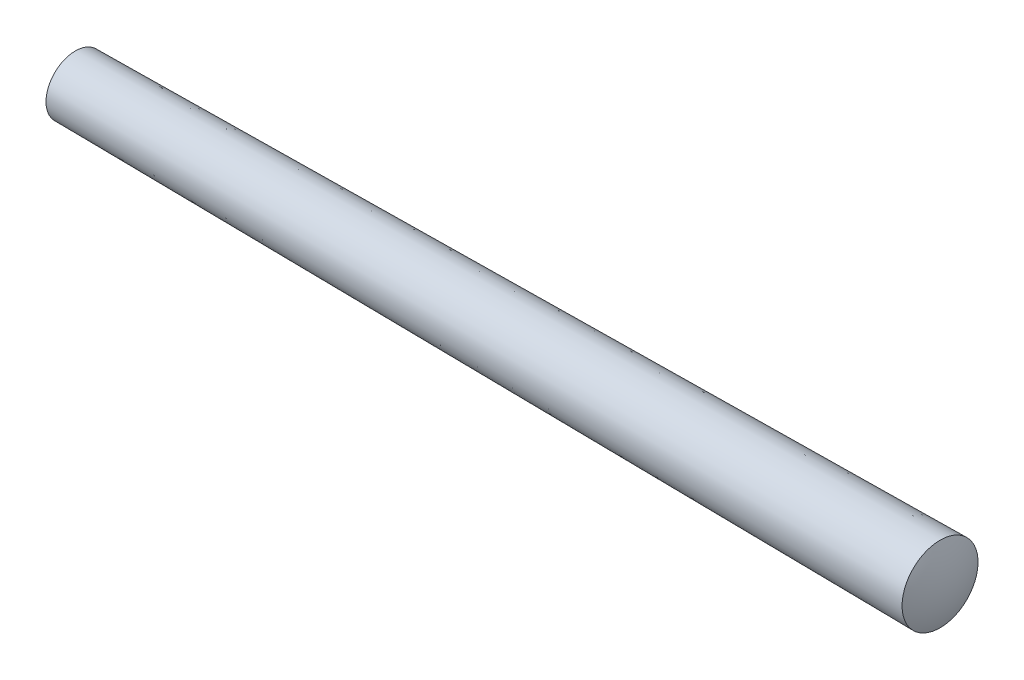
SolidWorks part; units mm, degrees
ref_plane "Plane1" through (0, 0, 0) normal (0, 0, 1) x (1, 0, 0)
ref_plane "Plane2" through (0, 0, 0) normal (0, 1, 0) x (1, 0, 0)
ref_plane "Plane3" through (0, 0, 0) normal (1, 0, 0) x (0, 0, -1)
other "Configuration Table"
sketch "Sketch1" plane through (0, 0, 0) normal (0, 0, 1) x (1, 0, 0)
  line L0 (0, 0) -> (210, 0) construction
  line L2 (0.4, 1.5) -> (44.6, 1.942)
  line L4 (0, 0) -> (45, 0)
  line L5 (0.4, -1.5) -> (44.6, -1.942) construction
  arc A0 (0.4, 1.5) -> (0, 0) centre (3.0125, 0) ccw
  arc A1 (44.6, 1.942) -> (45, 0) centre (40.0858, 0) cw
  dimension "Diameter" = 3
  dimension "D1" = 0.4
  dimension "D2" = 0.573
revolve "Base-Revolve" add sketch "Sketch1" angle 360 about L0
equation "\"D1@Sketch1\" = \"Crown_ht@Sketch1\""
